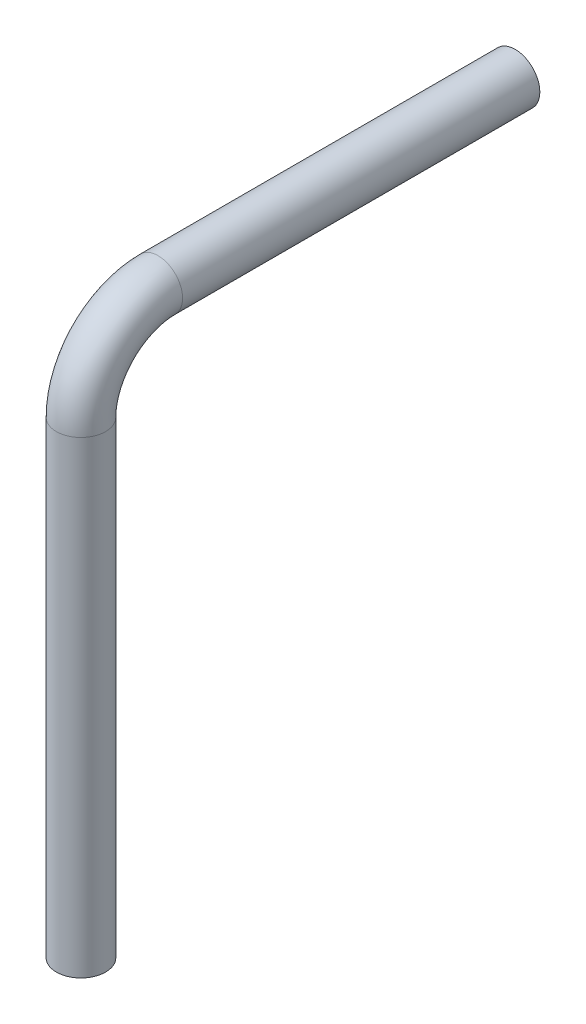
SolidWorks part; units mm, degrees
ref_plane "Front Plane" through (0, 0, 0) normal (0, 0, 1) x (1, 0, 0)
ref_plane "Top Plane" through (0, 0, 0) normal (0, 1, 0) x (1, 0, 0)
ref_plane "Right Plane" through (0, 0, 0) normal (1, 0, 0) x (0, 0, -1)
sketch "Sketch1" plane through (0, 0, 0) normal (0, 1, 0) x (1, 0, 0)
  circle A0 centre (0, 0) radius 8
  circle A1 centre (0, 0) radius 6
sketch3d "3DSketch1"
  line L0 (0, 0, 0) -> (0, 152, 0)
  line L1 (0, 177, -25) -> (0, 177, -141)
  arc A0 (0, 152, 0) -> (0, 177, -25) centre (0, 152, -25) cw
  point P4 (-25, 152, -25)
sweep "Sweep1" add path "3DSketch1" circular profile diameter 16 parameters "D3"=16
sweep "Hollow_tube_OD_and_wall_PROVISIONAL" cut path "3DSketch1<2>" circular profile diameter 12 parameters "D3"=12
sketch3d "3DSketch1<2>" same geometry as "3DSketch1"
